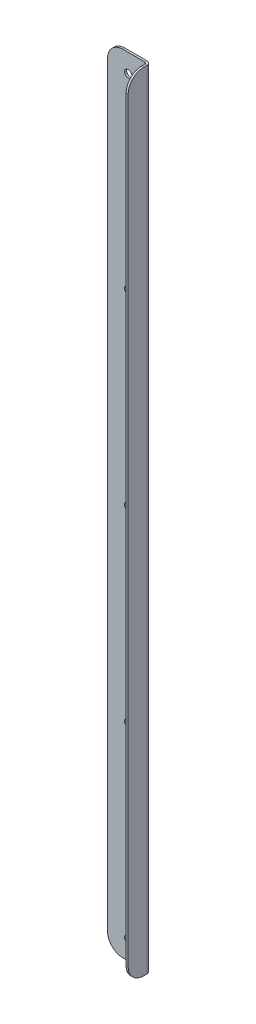
SolidWorks part; units mm, degrees
note: The reader was unsure of these and kept them because the rebuilt part matched: flange length of "Edge-Flange1".
material "AISI 316 Stainless Steel Sheet (SS)"
ref_plane "Front Plane" through (0, 0, 0) normal (0, 0, 1) x (1, 0, 0)
ref_plane "Top Plane" through (0, 0, 0) normal (0, 1, 0) x (1, 0, 0)
ref_plane "Right Plane" through (0, 0, 0) normal (1, 0, 0) x (0, 0, -1)
sketch "Sketch2" plane through (0, 0, 0) normal (0, 0, 1) x (1, 0, 0)
  line L1 (-20, -380.5) -> (20, -380.5)
  line L2 (-20, -380.5) -> (-20, 380.5)
  line L3 (-20, 380.5) -> (20, 380.5)
  line L4 (20, -380.5) -> (20, 380.5)
  line L5 (-20, -380.5) -> (20, 380.5) construction
  line L6 (-20, 380.5) -> (20, -380.5) construction
  point P0 (0, 0)
  dimension "D1" = 40
  dimension "D2" = 761
base flange "Base-Flange1" sketch "Sketch2" thickness 2 reverse thickness direction no parameters "D1"=1
edge flange "Edge-Flange1" sketch "Sketch9" flange angle 90 flange length 22 flange position material inside bend radius 2 thickness 2 relief rectangular parameters "D6"=10
sketch "Sketch9" plane through (20, 0, 0) normal (1, 0, 0) x (0, 1, 0)
  line L0 (-380.5, 0) -> (380.5, 0) construction
  line L1 (-380.5, 0) -> (380.5, 0)
  line L2 (-380.5, 0) -> (-380.5, 20)
  line L3 (-380.5, 20) -> (380.5, 20)
  line L4 (380.5, 20) -> (380.5, 0)
bend "EdgeBend1" bend radius 2 bend angle 90 parameters "D5"=1
fillet "Fillet1" radius 15 4 edges at (19, 380.5, 20) (-20, 380.5, -1) (-20, -380.5, -1) (19, -380.5, 20)
hole_wizard "Ø7.0 (7) Diameter Hole1" positions "Sketch10" profile "Sketch11" hole size "Ø7.0" standard "ISO" end condition through all
sketch "Sketch10" plane through (0, 0, 0) normal (0, 0, 1) x (1, 0, 0)
  line L0 (16, 380.5) -> (-5, 380.5) construction
  line L1 (16, 380.5) -> (16, -380.5) construction
  line L2 (0, 362.5) -> (0, 181.25) construction
  line L3 (0, 181.25) -> (0, 0) construction
  line L4 (0, 0) -> (0, -181.25) construction
  line L5 (0, -181.25) -> (0, -362.5) construction
  line L7 (-5, -380.5) -> (16, -380.5) construction
  point P0 (0, 362.5)
  point P2 (0, 181.25)
  point P4 (0, 0)
  point P7 (0, -181.25)
  point P9 (0, -362.5)
  dimension "D1" = 18
  dimension "D2" = 16
  dimension "D3" = 18
sketch "Sketch11" plane through (0, 362.5, 0) normal (1, 0, 0) x (0, -1, 0)
  line L0 (0, 0) -> (0, 2)
  line L1 (0, 2) -> (3.5, 2)
  line L2 (3.5, 2) -> (3.5, 0)
  line L5 (3.5, 0) -> (0, 0)
  line L11 (0, -6.35) -> (0, 107.95) construction
  dimension "Thru Hole Dia." = 7
  dimension "Thru Hole Depth" = 2
sketch "Bend-Lines1" [suppressed] plane through (0, 0, 0) normal (0, 1, 0) x (1, 0, 0)
sketch "Bounding-Box1" [suppressed] plane through (0, 0, 0) normal (0, 1, 0) x (1, 0, 0)
sheet metal parameters "Sheet-Metal1" thickness 2 parameters "D1"=1
flat pattern "Flat-Pattern1" [suppressed]
sketch "Bend-Lines2" plane through (0, 0, 0) normal (0, 1, 0) x (1, 0, 0)
sketch3d "Bounding-Box2" [suppressed]
  line L0 (-30, 390, 0) -> (-30, -390, 0) construction
  line L1 (30, 390, 0) -> (30, -390, 0) construction
  line L2 (-30, 390, 0) -> (30, 390, 0) construction
  line L3 (-30, -390, 0) -> (30, -390, 0) construction
sheet metal parameters "Sheet-Metal2" thickness 2 parameters "D1"=1
flat pattern "Flat-Pattern1"
sketch "Bend-Lines2" plane through (0, 0, 0) normal (0, 0, 1) x (1, 0, 0)
  line L0 (18.3562, -380.5) -> (18.3562, 380.5) construction
  line L1 (18.3562, -380.5) -> (18.3562, 380.5) construction
sketch3d "Bounding-Box2" [suppressed]
  line L0 (51.7124, -380.5, 0) -> (51.7124, 380.5, 0) construction
  line L1 (-20, -380.5, 0) -> (-20, 380.5, 0) construction
  line L2 (51.7124, -380.5, 0) -> (-20, -380.5, 0) construction
  line L3 (51.7124, 380.5, 0) -> (-20, 380.5, 0) construction
bend of the flat pattern "Flatten-<EdgeBend1>1"
sheet metal parameters "Sheet-Metal5" thickness 2 parameters "D1"=1
flat pattern "Flat-Pattern1"
sketch "Bend-Lines2" plane through (0, 0, 0) normal (0, 0, 1) x (1, 0, 0)
  line L0 (18.3562, -380.5) -> (18.3562, 380.5) construction
  line L1 (18.3562, -380.5) -> (18.3562, 380.5) construction
sketch3d "Bounding-Box2" [suppressed]
  line L0 (38.7124, -380.5, 0) -> (38.7124, 380.5, 0) construction
  line L1 (-20, -380.5, 0) -> (-20, 380.5, 0) construction
  line L2 (38.7124, -380.5, 0) -> (-20, -380.5, 0) construction
  line L3 (38.7124, 380.5, 0) -> (-20, 380.5, 0) construction
bend of the flat pattern "Flatten-<EdgeBend1>1"
